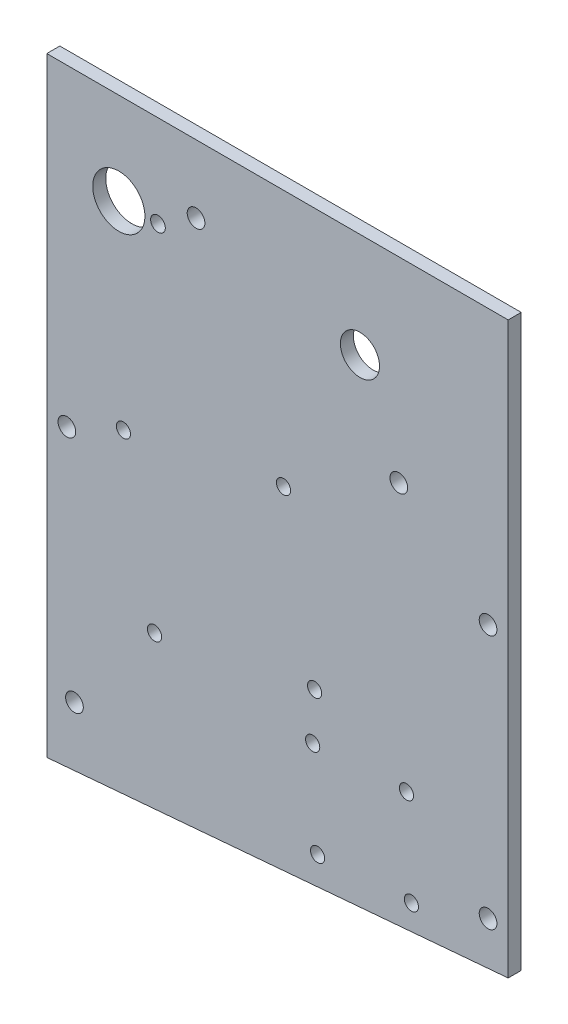
SolidWorks part; units mm, degrees
material "Acrylic (Medium-high impact)"
ref_plane "Front Plane" through (0, 0, 0) normal (0, 0, 1) x (1, 0, 0)
ref_plane "Top Plane" through (0, 0, 0) normal (0, 1, 0) x (1, 0, 0)
ref_plane "Right Plane" through (0, 0, 0) normal (1, 0, 0) x (0, 0, -1)
sketch "Sketch1" plane through (0, 0, 0) normal (0, 0, 1) x (1, 0, 0)
  line L4 (112.268, 0) -> (0, 0)
  line L5 (0, 0) -> (0, -148.336)
  line L6 (0, -148.336) -> (112.268, -138.684)
  line L7 (112.268, -138.684) -> (112.268, 0)
  line L8 (112.268, 0) -> (0, 0)
  line L9 (0, 0) -> (0, -148.336)
  line L10 (0, -148.336) -> (112.268, -138.684)
  line L11 (112.268, -138.684) -> (112.268, 0)
  dimension "D1" = 0
extrude "Boss-Extrude1" add sketch "Sketch1" against normal blind 3.175
hole_wizard "#6 Clearance Hole1" positions "Sketch3" profile "Sketch2" hole size "#6" standard "ANSI Inch" end condition through all
sketch "Sketch3" plane through (0, 0, 0) normal (0, 0, 1) x (1, 0, 0)
  point P0 (6.731, -133.35)
  point P3 (107.3785, -128.5875)
  point P6 (107.3785, -66.675)
  point P9 (4.8895, -76.2)
sketch "Sketch2" plane through (6.731, -133.35, 0) normal (1, 0, 0) x (0, -1, 0)
  line L0 (0, 0) -> (0, 3.175)
  line L1 (0, 3.175) -> (2.1526, 3.175)
  line L2 (2.1526, 3.175) -> (2.1526, 0)
  line L5 (2.1526, 0) -> (0, 0)
  line L11 (0, -6.35) -> (0, 107.95) construction
  dimension "Thru Hole Dia." = 4.3053
  dimension "Thru Hole Depth" = 3.175
hole_wizard "#4 Clearance Hole1" positions "Sketch5" profile "Sketch4" hole size "#4" standard "ANSI Inch" end condition through all
sketch "Sketch5" plane through (0, 0, 0) normal (0, 0, 1) x (1, 0, 0)
  point P0 (18.6445, -70.0322)
  point P3 (57.6028, -62.4595)
  point P6 (65.1755, -101.4178)
  point P9 (26.2172, -108.9905)
  point P12 (65.8919, -135.8375)
  point P15 (88.7205, -134.6411)
  point P18 (87.5241, -111.8125)
  point P21 (64.6955, -113.0089)
sketch "Sketch4" plane through (18.6445, -70.0322, 0) normal (1, 0, 0) x (0, -1, 0)
  line L0 (0, 0) -> (0, 3.175)
  line L1 (0, 3.175) -> (1.7272, 3.175)
  line L2 (1.7272, 3.175) -> (1.7272, 0)
  line L5 (1.7272, 0) -> (0, 0)
  line L11 (0, -6.35) -> (0, 107.95) construction
  dimension "Thru Hole Dia." = 3.4544
  dimension "Thru Hole Depth" = 3.175
hole_wizard "#6 Clearance Hole2" positions "Sketch7" profile "Sketch6" hole size "#6" standard "ANSI Inch" end condition through all
sketch "Sketch7" plane through (0, 0, 0) normal (0, 0, 1) x (1, 0, 0)
  point P0 (36.322, -16.51)
  point P3 (85.6615, -47.625)
sketch "Sketch6" plane through (36.322, -16.51, 0) normal (1, 0, 0) x (0, -1, 0)
  line L0 (0, 0) -> (0, 3.175)
  line L1 (0, 3.175) -> (2.1526, 3.175)
  line L2 (2.1526, 3.175) -> (2.1526, 0)
  line L5 (2.1526, 0) -> (0, 0)
  line L11 (0, -6.35) -> (0, 107.95) construction
  dimension "Thru Hole Dia." = 4.3053
  dimension "Thru Hole Depth" = 3.175
hole_wizard "9/64 (0.14063) Diameter Hole1" positions "Sketch9" profile "Sketch8" hole size "9/64" standard "ANSI Inch" end condition through all
sketch "Sketch9" plane through (0, 0, 0) normal (0, 0, 1) x (1, 0, 0)
  point P0 (27.051, -22.352)
sketch "Sketch8" plane through (27.051, -22.352, 0) normal (1, 0, 0) x (0, -1, 0)
  line L0 (0, 0) -> (0, 3.175)
  line L1 (0, 3.175) -> (1.786, 3.175)
  line L2 (1.786, 3.175) -> (1.786, 0)
  line L5 (1.786, 0) -> (0, 0)
  line L11 (0, -6.35) -> (0, 107.95) construction
  dimension "Thru Hole Dia." = 3.572
  dimension "Thru Hole Depth" = 3.175
hole_wizard "3/8 (0.375) Diameter Hole1" positions "Sketch11" profile "Sketch10" hole size "3/8" standard "ANSI Inch" end condition through all
sketch "Sketch11" plane through (0, 0, 0) normal (0, 0, 1) x (1, 0, 0)
  point P0 (76.2, -25.4)
sketch "Sketch10" plane through (76.2, -25.4, 0) normal (1, 0, 0) x (0, -1, 0)
  line L0 (0, 0) -> (0, 3.175)
  line L1 (0, 3.175) -> (4.7625, 3.175)
  line L2 (4.7625, 3.175) -> (4.7625, 0)
  line L5 (4.7625, 0) -> (0, 0)
  line L11 (0, -6.35) -> (0, 107.95) construction
  dimension "Thru Hole Dia." = 9.525
  dimension "Thru Hole Depth" = 3.175
hole_wizard "1/2 (0.5) Diameter Hole1" positions "Sketch13" profile "Sketch12" hole size "1/2" standard "ANSI Inch" end condition through all
sketch "Sketch13" plane through (0, 0, 0) normal (0, 0, 1) x (1, 0, 0)
  point P0 (17.526, -22.352)
sketch "Sketch12" plane through (17.526, -22.352, 0) normal (1, 0, 0) x (0, -1, 0)
  line L0 (0, 0) -> (0, 3.175)
  line L1 (0, 3.175) -> (6.35, 3.175)
  line L2 (6.35, 3.175) -> (6.35, 0)
  line L5 (6.35, 0) -> (0, 0)
  line L11 (0, -6.35) -> (0, 107.95) construction
  dimension "Thru Hole Dia." = 12.7
  dimension "Thru Hole Depth" = 3.175
